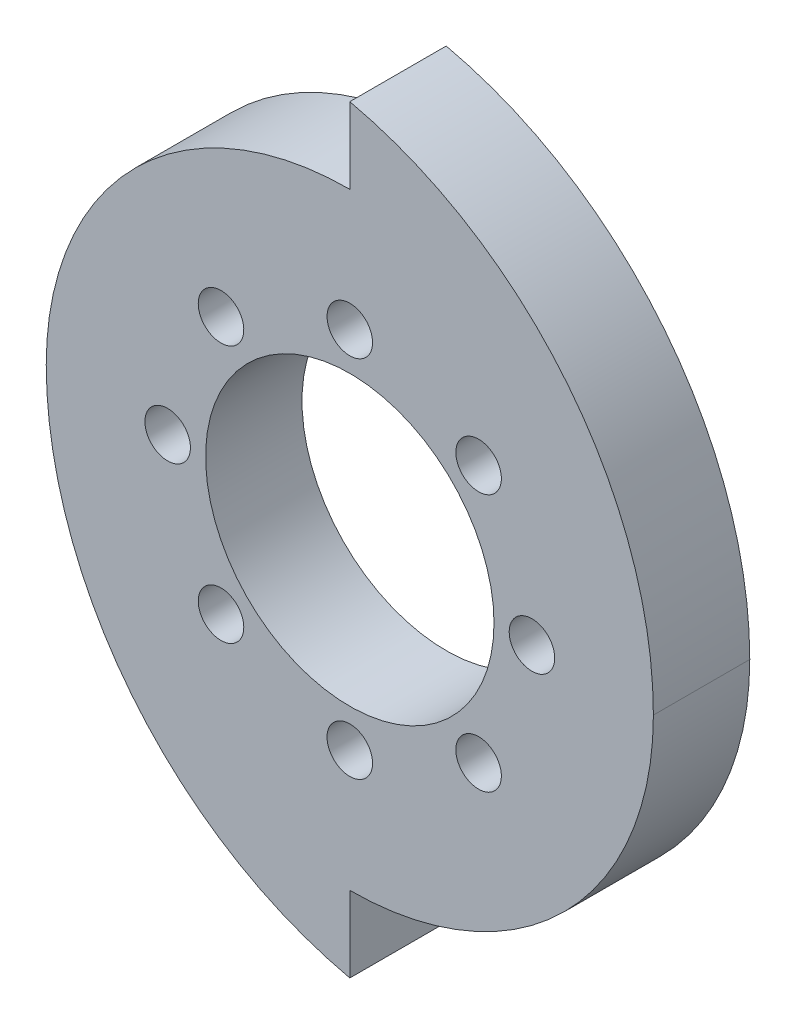
SolidWorks part; units mm, degrees
material "AISI 316 Stainless Steel Sheet (SS)"
ref_plane "Front Plane" through (0, 0, 0) normal (0, 0, 1) x (1, 0, 0)
ref_plane "Top Plane" through (0, 0, 0) normal (0, 1, 0) x (1, 0, 0)
ref_plane "Right Plane" through (0, 0, 0) normal (1, 0, 0) x (0, 0, -1)
sketch "Sketch3" plane through (0, 0, 0) normal (0, 0, 1) x (1, 0, 0)
  line L5 (0, 20) -> (0, 25)
  line L12 (0, -20) -> (0, -25)
  arc A9 (0, 25) -> (-20, 0) centre (5.625, 0) ccw construction
  arc A11 (0, -25) -> (20, 0) centre (-5.625, 0) ccw construction
  arc A14 (0, 25) -> (20, 0) centre (-5.625, 0) cw
  arc A15 (0, -25) -> (-20, 0) centre (5.625, 0) cw
  arc A16 (0, 20) -> (-20, 0) centre (0, 0) ccw
  arc A17 (20, 0) -> (0, -20) centre (0, 0) cw
  point P5 (20, -0.0522)
  point P7 (20.0691, -0.3601)
  point P9 (0, -22.7602)
  point P10 (0, 0)
  point P11 (0, 0)
  point P12 (0, 0)
  point P18 (0, 0)
  point P19 (0, 0)
  dimension "D2" = 5
  dimension "D1" = 40
extrude "Boss-Extrude1" add sketch "Sketch3" along normal blind 6.35
sketch "Sketch4" plane through (0, 0, 6.35) normal (0, 0, 1) x (1, 0, 0)
  circle A10 centre (0, 0) radius 9.5
  circle A11 centre (0, 12) radius 1.5
  dimension "D2" = 12
  dimension "D3" = 19
  dimension "D1" = 3
extrude "Cut-Extrude1" cut sketch "Sketch4" against normal through all
ref_axis "Axis1" through (0, 0, -0.475) along (0, 0, 1)
pattern_circular "CirPattern1" count 8 over 360 about axis through (0, 0, -0.475) along (0, 0, 1) of "Cut-Extrude1"
